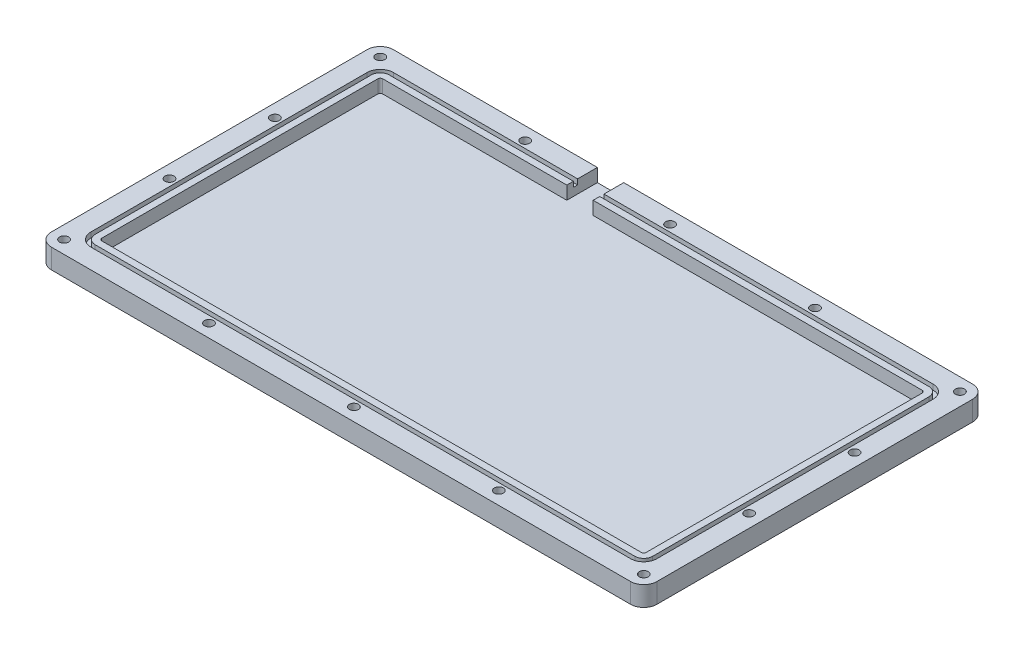
SolidWorks part; units mm, degrees
ref_plane "Front Plane" through (0, 0, 0) normal (0, 0, 1) x (1, 0, 0)
ref_plane "Top Plane" through (0, 0, 0) normal (0, 1, 0) x (1, 0, 0)
ref_plane "Right Plane" through (0, 0, 0) normal (1, 0, 0) x (0, 0, -1)
sketch "Sketch1" plane through (0, 0, 0) normal (0, 1, 0) x (1, 0, 0)
  line L1 (0, 0) -> (291.846, 0)
  line L2 (0, 0) -> (0, 164.846)
  line L3 (0, 164.846) -> (291.846, 164.846)
  line L4 (291.846, 0) -> (291.846, 164.846)
  dimension "D1" = 164.846
  dimension "D2" = 291.846
extrude "Boss-Extrude1" add sketch "Sketch1" along normal blind 9.525
fillet "Fillet1" radius 6.35 4 edges at (291.846, 4.7625, 0) (291.846, 4.7625, -164.846) (0, 4.7625, 0) (0, 4.7625, -164.846)
sketch "Sketch2" plane through (0, 0, 0) normal (0, -1, 0) x (1, 0, 0)
  line L0 (134.4333, -6.223) -> (134.4333, 0) construction
  line L1 (6.223, -6.223) -> (285.623, -6.223) construction
  line L2 (6.223, -6.223) -> (6.223, -158.623) construction
  line L3 (6.223, -158.623) -> (285.623, -158.623) construction
  line L4 (285.623, -6.223) -> (285.623, -158.623) construction
  line L5 (6.35, 0) -> (285.496, 0) construction
  line L6 (6.223, -49.1425) -> (0, -49.1425) construction
  line L7 (0, -158.496) -> (0, -6.35) construction
  line L8 (117.1513, -158.623) -> (117.1513, -164.846) construction
  line L9 (285.496, -164.846) -> (6.35, -164.846) construction
  line L10 (285.623, -107.7439) -> (291.846, -107.7439) construction
  line L11 (291.846, -6.35) -> (291.846, -158.496) construction
  circle A0 centre (6.223, -6.223) radius 2.1844
  circle A1 centre (285.623, -6.223) radius 2.1844
  circle A2 centre (6.223, -158.623) radius 2.1844
  circle A3 centre (285.623, -158.623) radius 2.1844
  dimension "D3" = 4.3688
  dimension "D1" = 279.4
  dimension "D2" = 152.4
extrude "Cut-Extrude1" cut sketch "Sketch2" against normal through all
chamfer "Chamfer1" distance 2.54 angle 41 4 edges at (6.223, 0, -8.4074) (285.623, 0, -8.4074) (285.623, 0, -160.8074) (6.223, 0, -160.8074) first distance on face at (285.623, 0, -160.8074)
pattern_linear "LPattern1" count 3 spacing 50.8 along (0, 0, -1) of face at (6.223, 2.208, -8.4074) of face at (6.223, 0, -10.9474) of face at (285.623, 2.208, -8.4074) of face at (285.623, 0, -10.9474)
pattern_linear "LPattern2" count 4 spacing 69.85 along (1, 0, 0) of face at (6.223, 2.208, -8.4074) of face at (6.223, 0, -10.9474) of face at (6.223, 2.208, -160.8074) of face at (6.223, 0, -163.3474)
sketch "Sketch3" plane through (0, 9.525, 0) normal (0, 1, 0) x (1, 0, 0)
  line L0 (6.35, 0) -> (285.496, 0) construction
  line L1 (275.971, 9.525) -> (15.875, 9.525)
  line L2 (282.321, 15.875) -> (282.321, 148.971)
  line L3 (275.971, 155.321) -> (15.875, 155.321)
  line L4 (9.525, 15.875) -> (9.525, 148.971)
  line L5 (291.846, 6.35) -> (291.846, 158.496) construction
  line L6 (285.496, 164.846) -> (6.35, 164.846) construction
  line L7 (0, 158.496) -> (0, 6.35) construction
  line L8 (275.971, 11.557) -> (15.875, 11.557)
  line L9 (11.557, 15.875) -> (11.557, 148.971)
  line L10 (275.971, 153.289) -> (15.875, 153.289)
  line L11 (280.289, 15.875) -> (280.289, 148.971)
  arc A0 (15.875, 9.525) -> (9.525, 15.875) centre (15.875, 15.875) cw
  arc A1 (15.875, 155.321) -> (9.525, 148.971) centre (15.875, 148.971) ccw
  arc A2 (282.321, 148.971) -> (275.971, 155.321) centre (275.971, 148.971) ccw
  arc A3 (275.971, 9.525) -> (282.321, 15.875) centre (275.971, 15.875) ccw
  arc A4 (15.875, 11.557) -> (11.557, 15.875) centre (15.875, 15.875) cw
  arc A5 (15.875, 153.289) -> (11.557, 148.971) centre (15.875, 148.971) ccw
  arc A6 (280.289, 148.971) -> (275.971, 153.289) centre (275.971, 148.971) ccw
  arc A7 (275.971, 11.557) -> (280.289, 15.875) centre (275.971, 15.875) ccw
  dimension "D5" = 6.35
  dimension "D1" = 9.525
  dimension "D2" = 9.525
  dimension "D3" = 9.525
  dimension "D4" = 9.525
  dimension "D6" = 2.032
extrude "Cut-Extrude3" cut sketch "Sketch3" against normal blind 2.54 contours L1 A3 L2 A2 L3 A1 L4 A0 A7 L8 A4 L9 A5 L10 A6 L11 region at (145.923, 9.525, -9.8343)
sketch "Sketch4" plane through (0, 9.525, 0) normal (0, 1, 0) x (1, 0, 0)
  line L24 (14.732, 148.971) -> (14.732, 15.875)
  line L25 (275.971, 150.114) -> (15.875, 150.114)
  line L26 (277.114, 15.875) -> (277.114, 148.971)
  line L27 (15.875, 14.732) -> (275.971, 14.732)
  line L28 (14.732, 148.971) -> (14.732, 15.875)
  line L29 (275.971, 150.114) -> (15.875, 150.114)
  line L30 (277.114, 15.875) -> (277.114, 148.971)
  line L31 (15.875, 14.732) -> (275.971, 14.732)
  arc A20 (15.875, 150.114) -> (14.732, 148.971) centre (15.875, 148.971) ccw
  arc A21 (14.732, 15.875) -> (15.875, 14.732) centre (15.875, 15.875) ccw
  arc A22 (277.114, 148.971) -> (275.971, 150.114) centre (275.971, 148.971) ccw
  arc A23 (275.971, 14.732) -> (277.114, 15.875) centre (275.971, 15.875) ccw
  arc A24 (15.875, 150.114) -> (14.732, 148.971) centre (15.875, 148.971) ccw
  arc A25 (14.732, 15.875) -> (15.875, 14.732) centre (15.875, 15.875) ccw
  arc A26 (277.114, 148.971) -> (275.971, 150.114) centre (275.971, 148.971) ccw
  arc A27 (275.971, 14.732) -> (277.114, 15.875) centre (275.971, 15.875) ccw
  dimension "D1" = 3.175
extrude "Cut-Extrude4" cut sketch "Sketch4" against normal blind 6.35
sketch "Sketch5" plane through (0, 0, -164.846) normal (0, 0, -1) x (-1, 0, 0)
  line L2 (-285.496, 9.525) -> (-6.35, 9.525) construction
  line L3 (-117.348, 3.175) -> (-104.648, 3.175)
  line L4 (-117.348, 3.175) -> (-117.348, 9.525)
  line L5 (-117.348, 9.525) -> (-104.648, 9.525)
  line L6 (-104.648, 3.175) -> (-104.648, 9.525)
  line L7 (0, 9.525) -> (0, 0) construction
  dimension "D2" = 6.35
  dimension "D1" = 12.7
  dimension "D3" = 104.648
extrude "Cut-Extrude5" cut sketch "Sketch5" against normal up to surface (14.732 mm away) up to face at (145.923, 6.35, -150.114)
